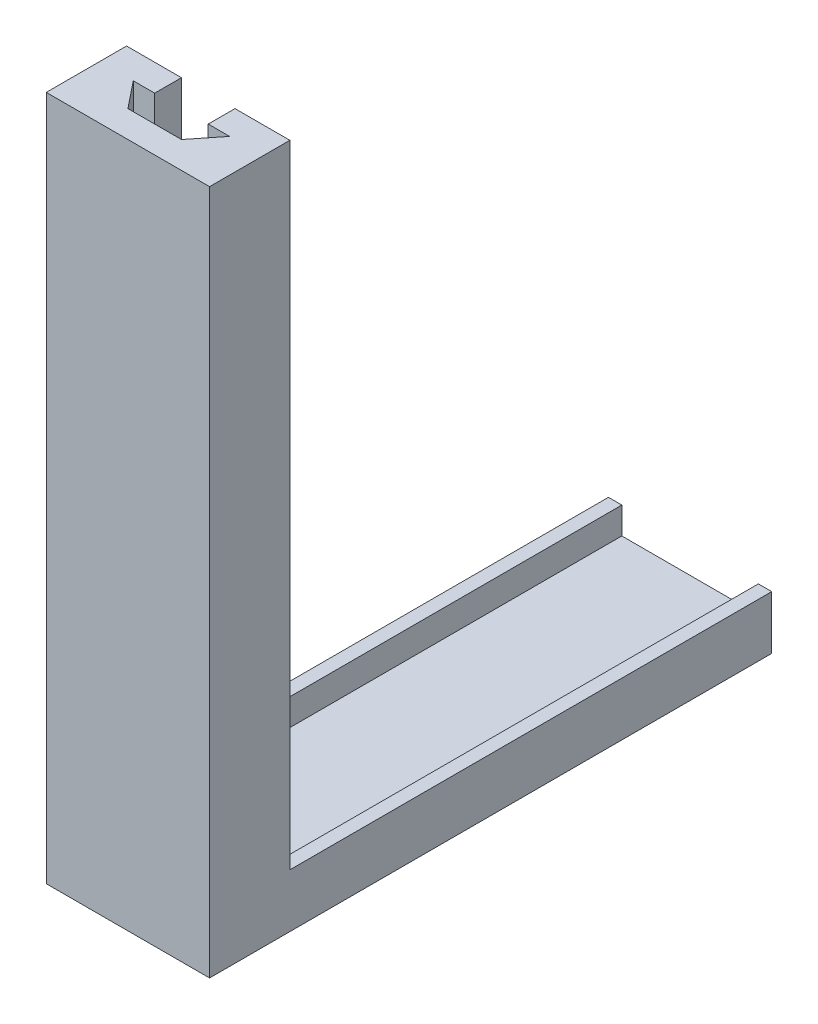
SolidWorks part; units mm, degrees
ref_plane "Front Plane" through (0, 0, 0) normal (0, 0, 1) x (1, 0, 0)
ref_plane "Top Plane" through (0, 0, 0) normal (0, 1, 0) x (1, 0, 0)
ref_plane "Right Plane" through (0, 0, 0) normal (1, 0, 0) x (0, 0, -1)
sketch "Sketch1" plane through (0, 0, 0) normal (0, 1, 0) x (1, 0, 0)
  line L1 (-15.25, -52.5) -> (15.25, -52.5)
  line L2 (-15.25, -52.5) -> (-15.25, 52.5)
  line L3 (-15.25, 52.5) -> (15.25, 52.5)
  line L4 (15.25, -52.5) -> (15.25, 52.5)
  line L5 (-15.25, -52.5) -> (15.25, 52.5) construction
  line L6 (-15.25, 52.5) -> (15.25, -52.5) construction
  point P0 (0, 0)
  dimension "D1" = 30.5
  dimension "D2" = 105
extrude "Boss-Extrude1" add sketch "Sketch1" along normal blind 10
sketch "Sketch2" plane through (0, 10, 0) normal (0, 1, 0) x (1, 0, 0)
  line L0 (15.25, -52.5) -> (15.25, 52.5) construction
  line L1 (-15.25, -52.5) -> (15.25, -52.5)
  line L2 (-15.25, -52.5) -> (-15.25, -37.5)
  line L3 (-15.25, -37.5) -> (15.25, -37.5)
  line L4 (15.25, -52.5) -> (15.25, -37.5)
  dimension "D1" = 15
extrude "Boss-Extrude2" add sketch "Sketch2" along normal blind 118
sketch "Sketch5" plane through (0, 10, 0) normal (0, 1, 0) x (1, 0, 0)
  line L0 (15.25, 52.5) -> (-15.25, 52.5) construction
  line L1 (12.75, 52.5) -> (-12.75, 52.5)
  line L2 (12.75, 52.5) -> (12.75, -37.5)
  line L3 (12.75, -37.5) -> (-12.75, -37.5)
  line L4 (-12.75, 52.5) -> (-12.75, -37.5)
  line L5 (15.25, -37.5) -> (-15.25, -37.5) construction
  line L6 (0, 52.5) -> (0, -37.5) construction
  line L7 (-15.25, 52.5) -> (-15.25, -37.5) construction
  dimension "D1" = 25.5
  dimension "D2" = 2.5
extrude "Cut-Extrude2" cut sketch "Sketch5" against normal blind 5
sketch "Sketch6" plane through (0, 128, 0) normal (0, 1, 0) x (1, 0, 0)
  line L0 (15.25, -37.5) -> (-15.25, -37.5) construction
  line L1 (-5, -37.5) -> (5, -37.5)
  line L2 (-5, -37.5) -> (-5, -42.5)
  line L4 (5, -37.5) -> (5, -42.5)
  line L5 (0, -37.5) -> (0, -52.5) construction
  line L6 (-15.25, -52.5) -> (15.25, -52.5) construction
  line L9 (-5, -42.5) -> (-9, -42.5)
  line L10 (-9, -42.5) -> (-5, -47.5)
  line L11 (-5, -47.5) -> (5, -47.5)
  line L12 (5, -42.5) -> (9, -42.5)
  line L13 (9, -42.5) -> (5, -47.5)
  dimension "D1" = 10
  dimension "D2" = 5
  dimension "D3" = 5
  dimension "D4" = 4
extrude "Cut-Extrude3" cut sketch "Sketch6" against normal blind 123
